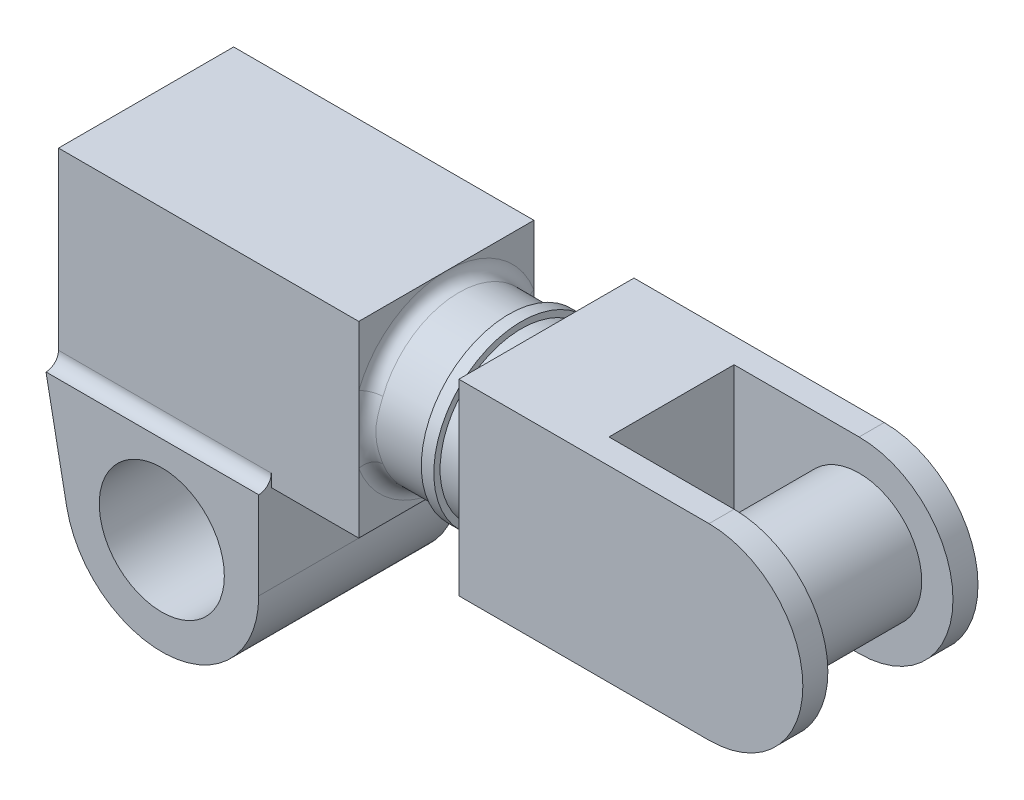
SolidWorks part; units mm, degrees
ref_plane "Alzado" through (0, 0, 0) normal (0, 0, 1) x (1, 0, 0)
ref_plane "Planta" through (0, 0, 0) normal (0, 1, 0) x (1, 0, 0)
ref_plane "Vista lateral" through (0, 0, 0) normal (1, 0, 0) x (0, 0, -1)
sketch "Croquis2" plane through (0, 0, 0) normal (1, 0, 0) x (0, 0, -1)
  line L1 (-70, 75) -> (70, 75)
  line L2 (-70, 75) -> (-70, -75)
  line L3 (-70, -75) -> (70, -75)
  line L4 (70, 75) -> (70, -75)
  line L5 (-70, 75) -> (70, -75) construction
  line L6 (-70, -75) -> (70, 75) construction
  point P0 (0, 0)
  dimension "D1" = 150
  dimension "D2" = 140
extrude "Saliente-Extruir2" add sketch "Croquis2" along normal blind 240
sketch "Croquis3" plane through (240, 0, 0) normal (1, 0, 0) x (0, 0, -1)
  circle A0 centre (0, 0) radius 65
  dimension "D1" = 130
extrude "Saliente-Extruir3" add sketch "Croquis3" along normal blind 50
sketch "Croquis4" plane through (290, 0, 0) normal (1, 0, 0) x (0, 0, -1)
  circle A0 centre (0, 0) radius 70
  dimension "D1" = 140
extrude "Saliente-Extruir4" add sketch "Croquis4" along normal blind 10
sketch "Croquis5" plane through (0, 0, 0) normal (0, 0, 1) x (1, 0, 0)
  line L0 (0, -75) -> (16.5223, -160)
  line L1 (0, 75) -> (0, -75) construction
  line L2 (170.0569, -145) -> (170.0569, -75)
  line L3 (240, -75) -> (0, -75) construction
  line L4 (0, -75) -> (170.0569, -75)
  arc A0 (16.5223, -160) -> (170.0569, -145) centre (92.5569, -145) ccw
  circle A1 centre (92.5569, -145) radius 50
  dimension "D1" = 155
  dimension "D2" = 100
  dimension "D3" = 191
  dimension "D4" = 85
  dimension "D5" = 70
extrude "Saliente-Extruir5" add sketch "Croquis5" along normal mid plane 160
fillet "Redondeo2" radius 10 3 edges at (85.0284, -75, -70) (85.0284, -75, 70) (240, 0, -65)
sketch "Croquis6" plane through (300, 0, 0) normal (1, 0, 0) x (0, 0, -1)
  circle A0 centre (0, 0) radius 65
  dimension "D1" = 130
extrude "Saliente-Extruir6" add sketch "Croquis6" along normal blind 20
sketch "Croquis7" plane through (0, 0, 0) normal (0, 0, 1) x (1, 0, 0)
  line L0 (520, 75) -> (320, 75)
  line L1 (320, 75) -> (320, -75)
  line L2 (320, -75) -> (520, -75)
  line L3 (320, -65) -> (320, 65) construction
  arc A0 (520, -75) -> (520, 75) centre (520, 0) ccw
  dimension "D1" = 150
  dimension "D2" = 200
extrude "Saliente-Extruir7" add sketch "Croquis7" along normal mid plane 140
sketch "Croquis8" plane through (0, 0, 0) normal (0, 0, 1) x (1, 0, 0)
  line L0 (520, 75) -> (420, 75)
  line L1 (520, 75) -> (320, 75) construction
  line L2 (420, 75) -> (420, -75)
  line L3 (320, -75) -> (520, -75) construction
  line L4 (420, -75) -> (520, -75)
  arc A0 (520, -75) -> (520, 75) centre (520, 0) ccw construction
  arc A1 (520, -75) -> (520, 75) centre (520, 0) ccw
extrude "Cortar-Extruir1" cut sketch "Croquis8" against normal mid plane 100
sketch "Croquis9" plane through (0, 0, -50) normal (0, 0, 1) x (1, 0, 0)
  circle A0 centre (520, 0) radius 50
  dimension "D1" = 100
extrude "Saliente-Extruir8" add sketch "Croquis9" along normal blind 100
